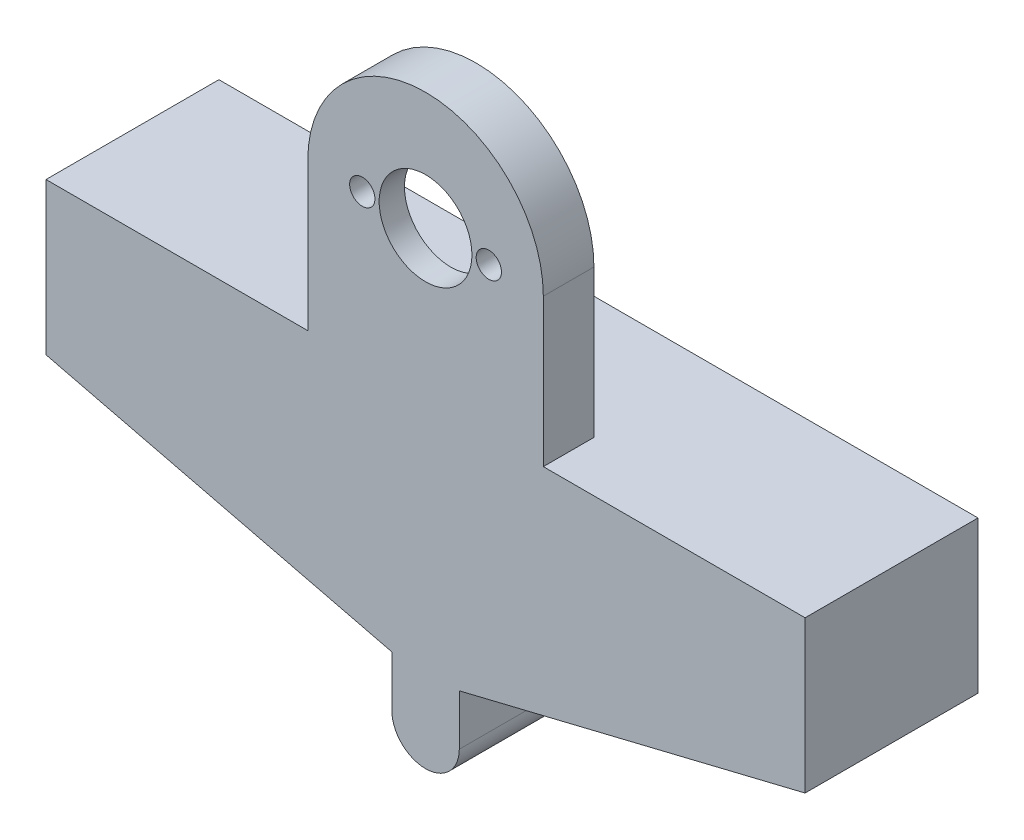
SolidWorks part; units mm, degrees
ref_plane "Front Plane" through (0, 0, 0) normal (0, 0, 1) x (1, 0, 0)
ref_plane "Top Plane" through (0, 0, 0) normal (0, 1, 0) x (1, 0, 0)
ref_plane "Right Plane" through (0, 0, 0) normal (1, 0, 0) x (0, 0, -1)
sketch "Sketch1" plane through (0, 0, 0) normal (0, 0, 1) x (1, 0, 0)
  line L0 (4, -9) -> (-4, -9)
  line L1 (-45, -9) -> (45, -9)
  line L2 (-45, -9) -> (-45, 9)
  line L3 (-45, 9) -> (45, 9)
  line L4 (45, -9) -> (45, 9)
  line L5 (-45, -9) -> (45, 9) construction
  line L6 (-45, 9) -> (45, -9) construction
  line L7 (-22.5, -3) -> (-7.5, -3)
  line L8 (-22.5, -3) -> (-22.5, 3)
  line L9 (-22.5, 3) -> (-7.5, 3)
  line L10 (-7.5, -3) -> (-7.5, 3)
  line L11 (-22.5, -3) -> (-7.5, 3) construction
  line L12 (-22.5, 3) -> (-7.5, -3) construction
  line L13 (7.5, -3) -> (22.5, -3)
  line L14 (7.5, -3) -> (7.5, 3)
  line L15 (7.5, 3) -> (22.5, 3)
  line L16 (22.5, -3) -> (22.5, 3)
  line L17 (7.5, -3) -> (22.5, 3) construction
  line L18 (7.5, 3) -> (22.5, -3) construction
  line L19 (4, -9) -> (4, -29)
  line L20 (-4, -9) -> (-4, -29)
  line L21 (4, -29) -> (-4, -29)
  line L22 (4, -19) -> (45, -9)
  line L23 (-4, -19) -> (-45, -9)
  point P0 (0, 0)
  point P6 (-15, 0)
  point P11 (15, 0)
  dimension "D1" = 90
  dimension "D2" = 18
  dimension "D3" = 6
  dimension "D4" = 6
  dimension "D5" = 6
  dimension "D6" = 6
  dimension "D7" = 15
  dimension "D8" = 15
  dimension "D9" = 7.5
  dimension "D10" = 7.5
  dimension "D11" = 8
  dimension "D12" = 4
  dimension "D13" = 20
extrude "Boss-Extrude1" add sketch "Sketch1" along normal blind 14 contours L1 L4 L3 L2 L0 L16 L13 L14 L15 L10 L7 L8 L9 | L21 L19 L0 L20 | L7 L10 L9 L8 | L13 L16 L15 L14 | L19 L22 L1 | L23 L20 L1 region at (0, -19, 0) region at (0, 0, 0) region at (17.6667, -12.3333, 0) region at (-17.6667, -12.3333, 0) region at (-15, 0, 0) region at (15, 0, 0)
sketch "Sketch3" plane through (0, 0, 0) normal (0, 0, 1) x (1, 0, 0)
  line L0 (4, -9) -> (-4, -9)
  line L1 (-45, -9) -> (45, -9)
  line L2 (-45, -9) -> (-45, 9)
  line L3 (-45, 9) -> (45, 9)
  line L4 (45, -9) -> (45, 9)
  line L5 (-45, -9) -> (45, 9) construction
  line L6 (-45, 9) -> (45, -9) construction
  line L7 (-22.5, -3) -> (-7.5, -3)
  line L8 (-22.5, -3) -> (-22.5, 3)
  line L9 (-22.5, 3) -> (-7.5, 3)
  line L10 (-7.5, -3) -> (-7.5, 3)
  line L11 (-22.5, -3) -> (-7.5, 3) construction
  line L12 (-22.5, 3) -> (-7.5, -3) construction
  line L13 (7.5, -3) -> (22.5, -3)
  line L14 (7.5, -3) -> (7.5, 3)
  line L15 (7.5, 3) -> (22.5, 3)
  line L16 (22.5, -3) -> (22.5, 3)
  line L17 (7.5, -3) -> (22.5, 3) construction
  line L18 (7.5, 3) -> (22.5, -3) construction
  line L19 (4, -9) -> (4, -29)
  line L20 (-4, -9) -> (-4, -29)
  line L21 (4, -29) -> (-4, -29)
  point P0 (0, 0)
  point P6 (-15, 0)
  point P11 (15, 0)
  dimension "D1" = 90
  dimension "D2" = 18
  dimension "D3" = 6
  dimension "D4" = 6
  dimension "D5" = 6
  dimension "D6" = 6
  dimension "D7" = 15
  dimension "D8" = 15
  dimension "D9" = 7.5
  dimension "D10" = 7.5
  dimension "D11" = 8
  dimension "D12" = 4
  dimension "D13" = 20
extrude "Boss-Extrude2" add sketch "Sketch3" against normal blind 6.5 contours L1 L4 L3 L2 L0 L16 L13 L14 L15 L10 L7 L8 L9 | L21 L19 L0 L20 region at (0, -19, 0) region at (0, 0, 0)
fillet "Fillet1" radius 4 2 edges at (-4, -29, 3.75) (4, -29, 3.75)
sketch "Sketch4" plane through (0, 0, 14) normal (0, 0, 1) x (1, 0, 0)
  line L0 (-13.9645, 26.5) -> (-13.9645, 9)
  line L1 (-45, 9) -> (45, 9) construction
  line L2 (13.9645, 26.5) -> (13.9645, 9)
  circle A0 centre (0, 26.5) radius 5.5
  circle A1 centre (7.5, 26.5) radius 1.5
  circle A2 centre (-7.5, 26.5) radius 1.5
  circle A3 centre (0, 26.5) radius 13.9645
  line M8 (45, 9) -> (-45, 9)
  dimension "D1" = 7.5
  dimension "D2" = 7.5
  dimension "D3" = 0
  dimension "D4" = 17.5
extrude "Boss-Extrude3" add sketch "Sketch4" against normal blind 6 contours A3 A0 A1 A2 | A3 L2 M8 | A3 L0 M8 region at (0, 12.2059, 14) region at (0, 40.0695, 14)
sketch "Sketch5" plane through (0, 0, 8) normal (0, 0, -1) x (-1, 0, 0)
  circle A2 centre (0, 26.5) radius 13
extrude "Cut-Extrude1" cut sketch "Sketch5" against normal blind 3
